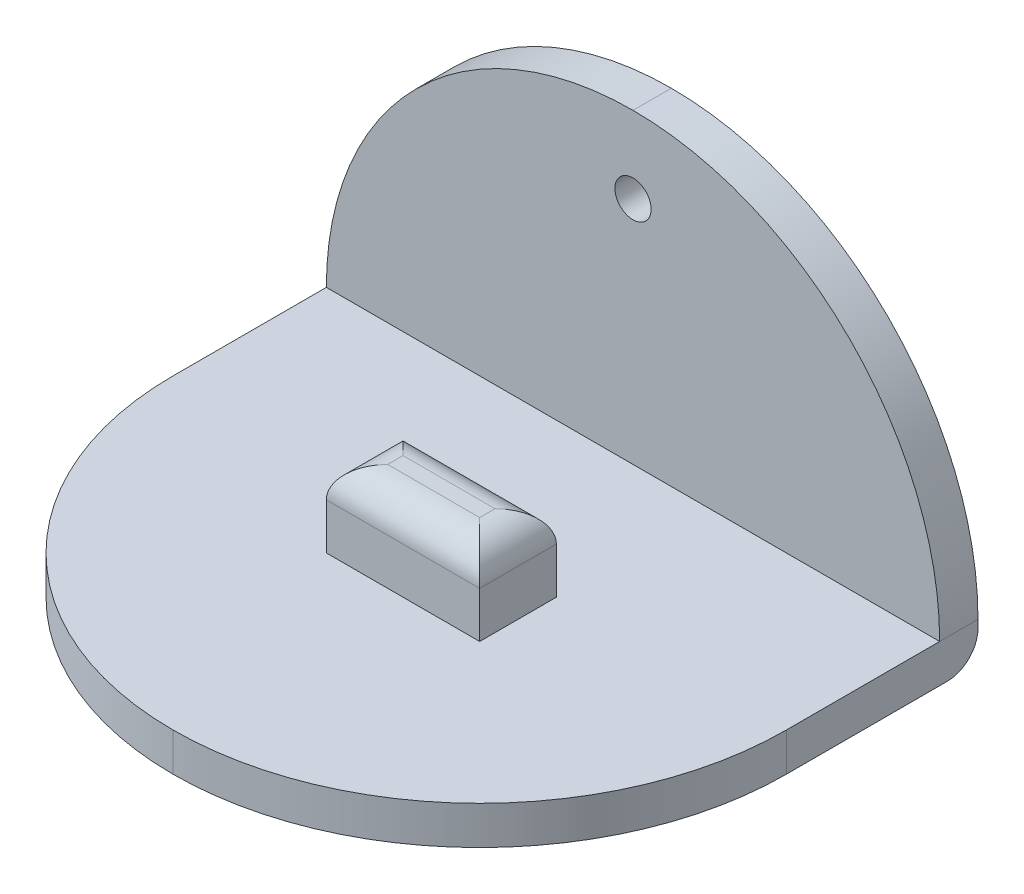
SolidWorks part; units mm, degrees
ref_plane "Front Plane" through (0, 0, 0) normal (0, 0, 1) x (1, 0, 0)
ref_plane "Top Plane" through (0, 0, 0) normal (0, 1, 0) x (1, 0, 0)
ref_plane "Right Plane" through (0, 0, 0) normal (1, 0, 0) x (0, 0, -1)
sketch "Sketch1" plane through (0, 0, 0) normal (1, 0, 0) x (0, 0, -1)
  line L0 (0, 0) -> (-41.275, 0)
  line L1 (-41.275, 0) -> (-41.275, 3.175)
  line L2 (-41.275, 3.175) -> (-3.175, 3.175)
  line L3 (-3.175, 3.175) -> (-3.175, 28.575)
  line L4 (-3.175, 28.575) -> (0, 28.575)
  line L5 (0, 28.575) -> (0, 0)
  dimension "D1" = 38.1
  dimension "D2" = 25.4
  dimension "D3" = 3.175
extrude "Boss-Extrude1" add sketch "Sketch1" along normal blind 50.8
sketch "Sketch2" plane through (0, 3.175, 0) normal (0, 1, 0) x (1, 0, 0)
  line L0 (50.8, -41.275) -> (0, -41.275) construction
  line L1 (19.05, -22.225) -> (31.75, -22.225)
  line L2 (19.05, -22.225) -> (19.05, -15.875)
  line L3 (19.05, -15.875) -> (31.75, -15.875)
  line L4 (31.75, -22.225) -> (31.75, -15.875)
  line L7 (50.8, -3.175) -> (0, -3.175) construction
  point P4 (25.4, -22.225)
  point P7 (25.4, -41.275)
  dimension "D1" = 6.35
  dimension "D2" = 12.7
  dimension "D3" = 12.7
extrude "Boss-Extrude2" add sketch "Sketch2" along normal blind 6.35
sketch "Sketch3" plane through (0, 0, 3.175) normal (0, 0, 1) x (1, 0, 0)
  line L0 (50.8, 28.575) -> (0, 28.575) construction
  line L1 (50.8, 3.175) -> (0, 3.175) construction
  circle A0 centre (25.4, 22.225) radius 1.5
  point P5 (25.4, 28.575)
  dimension "D1" = 3
  dimension "D2" = 19.05
extrude "Cut-Extrude1" cut sketch "Sketch3" against normal through all
fillet "Fillet1" radius 2.54 4 edges at (25.4, 9.525, 15.875) (31.75, 9.525, 19.05) (25.4, 9.525, 22.225) (19.05, 9.525, 19.05)
fillet "Fillet2" radius 25.4 4 edges at (0, 28.575, 1.5875) (50.8, 28.575, 1.5875) (50.8, 1.5875, 41.275) (0, 1.5875, 41.275)
fillet "Fillet3" radius 2.54 1 edges at (25.4, 0, 0)
